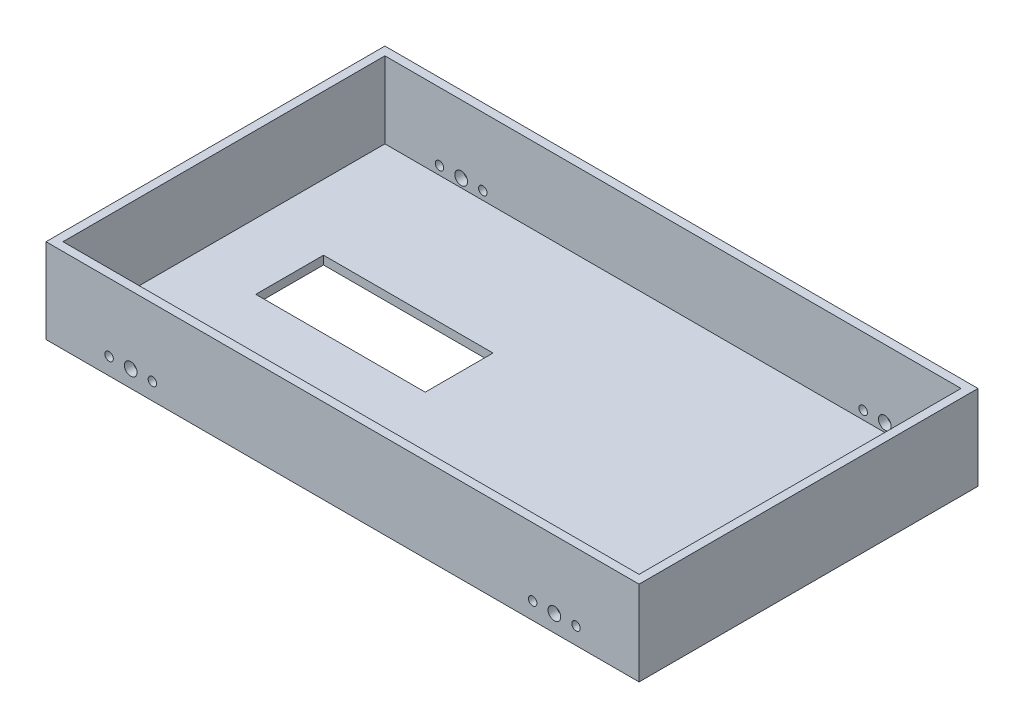
SolidWorks part; units mm, degrees
ref_plane "Front Plane" through (0, 0, 0) normal (0, 0, 1) x (1, 0, 0)
ref_plane "Top Plane" through (0, 0, 0) normal (0, 1, 0) x (1, 0, 0)
ref_plane "Right Plane" through (0, 0, 0) normal (1, 0, 0) x (0, 0, -1)
sketch "Sketch1" plane through (0, 0, 0) normal (0, 1, 0) x (1, 0, 0)
  line L1 (175, -100) -> (-175, -100)
  line L2 (175, -100) -> (175, 100)
  line L3 (175, 100) -> (-175, 100)
  line L4 (-175, -100) -> (-175, 100)
  line L5 (175, -100) -> (-175, 100) construction
  line L6 (175, 100) -> (-175, -100) construction
  point P0 (0, 0)
  dimension "D1" = 200
  dimension "D2" = 350
extrude "Boss-Extrude1" add sketch "Sketch1" along normal blind 50 contours L1 L4 L3 L2
shell "Shell1" thickness 5 removed face at (0, 50, 0)
sketch "Sketch3" plane through (0, 0, 100) normal (0, 0, 1) x (1, 0, 0)
  line L0 (0, -27.5) -> (0, 27.5) construction
  line L1 (-125, 10) -> (-125, 25.1535) construction
  line L2 (0, 0) -> (0, 67.0871) construction
  circle A0 centre (-125, 10) radius 3.75
  circle A1 centre (125, 10) radius 3.75
  circle A2 centre (-137.78, 10) radius 2.5
  circle A4 centre (-112.22, 10) radius 2.5
  circle A5 centre (112.22, 10) radius 2.5
  circle A6 centre (137.78, 10) radius 2.5
  dimension "BushingDiam" = 7.5
  dimension "M5" = 5
  dimension "DistanceFromCenter" = 125
  dimension "HeightWheel" = 10
  dimension "M5Dist" = 12.78
extrude "Cut-Extrude1" cut sketch "Sketch3" against normal up to surface (200 mm away) up to face at (0, 25, -100)
sketch "Sketch4" plane through (0, 5, 0) normal (0, 1, 0) x (1, 0, 0)
  line L0 (-170, -95) -> (-170, 95) construction
  line L1 (-131.2158, 20) -> (-31.2158, 20)
  line L2 (-131.2158, 20) -> (-131.2158, -20)
  line L3 (-131.2158, -20) -> (-31.2158, -20)
  line L4 (-31.2158, 20) -> (-31.2158, -20)
  dimension "D1" = 38.7842
  dimension "GearboxWidth" = 40
  dimension "GearboxLength" = 100
  dimension "D2" = 20
extrude "Cut-Extrude2" cut sketch "Sketch4" against normal through all
